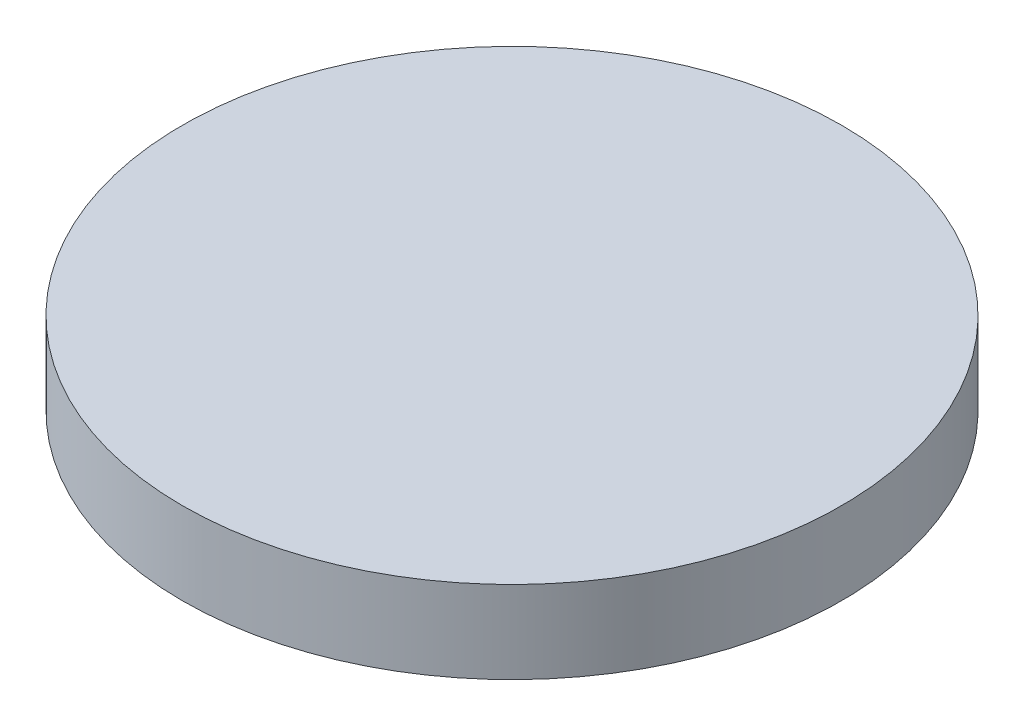
SolidWorks part; units mm, degrees
ref_plane "前视基准面" through (0, 0, 0) normal (0, 0, 1) x (1, 0, 0)
ref_plane "上视基准面" through (0, 0, 0) normal (0, 1, 0) x (1, 0, 0)
ref_plane "右视基准面" through (0, 0, 0) normal (1, 0, 0) x (0, 0, -1)
sketch "草图1" plane through (0, 0, 0) normal (0, 1, 0) x (1, 0, 0)
  circle A0 centre (0, 0) radius 40
  dimension "D1" = 80
extrude "凸台-拉伸1" add sketch "草图1" along normal blind 10
ref_axis "基准轴1" through (0, 10, 0) along (0, -1, 0)
